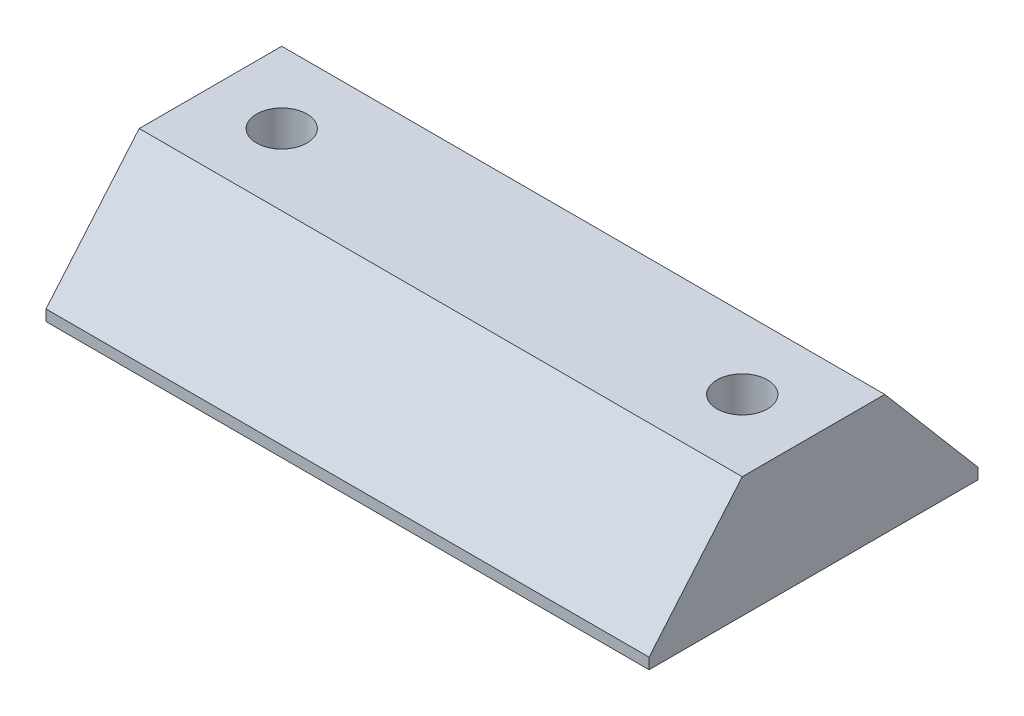
SolidWorks part; units mm, degrees
ref_plane "Front Plane" through (0, 0, 0) normal (0, 0, 1) x (1, 0, 0)
ref_plane "Top Plane" through (0, 0, 0) normal (0, 1, 0) x (1, 0, 0)
ref_plane "Right Plane" through (0, 0, 0) normal (1, 0, 0) x (0, 0, -1)
sketch "Sketch2" plane through (0, 0, 0) normal (0, 1, 0) x (1, 0, 0)
  line L1 (0, 0) -> (55, 0)
  line L2 (0, 0) -> (0, 30)
  line L3 (0, 30) -> (55, 30)
  line L4 (55, 0) -> (55, 30)
  dimension "D1" = 30
  dimension "D2" = 55
extrude "Boss-Extrude1" add sketch "Sketch2" along normal blind 11
chamfer "Chamfer1" distance 10 distance2 8.5 2 edges at (27.5, 11, -30) (27.5, 11, 0) first distance on face at (27.5, 5.5, -30) first distance on face at (27.5, 5.5, 0)
sketch "Sketch3" plane through (0, 11, 0) normal (0, 1, 0) x (1, 0, 0)
  line L0 (0, 21.5) -> (0, 8.5) construction
  line L1 (55, 21.5) -> (0, 21.5) construction
  line L2 (0, 8.5) -> (55, 8.5) construction
  line L3 (0, 0) -> (55, 0) construction
  line L4 (55, 30) -> (0, 30) construction
  circle A0 centre (6.5, 15) radius 2.3
  circle A1 centre (48.5, 15) radius 2.3
  dimension "D1" = 4.6
  dimension "D2" = 4.6
  dimension "D3" = 42
  dimension "D4" = 6.5
  dimension "D5" = 6.5
  dimension "D6" = 6.5
  dimension "D7" = 15
  dimension "D8" = 15
extrude "Cut-Extrude1" cut sketch "Sketch3" against normal up to next
sketch "Sketch4" plane through (0, 0, 0) normal (0, -1, 0) x (1, 0, 0)
  line L2 (16.5, -11.0975) -> (38.5, -11.0975)
  line L3 (16.5, -11.0975) -> (16.5, -18.8975)
  line L4 (16.5, -18.8975) -> (38.5, -18.8975)
  line L7 (38.5, -11.0975) -> (38.5, -18.8975)
  circle A0 centre (6.5, -15) radius 2.3 construction
  dimension "D5" = 3.8975
  dimension "D2" = 3.9025
  dimension "D1" = 7.8
extrude "Boss-Extrude2" add sketch "Sketch4" along normal blind 3
